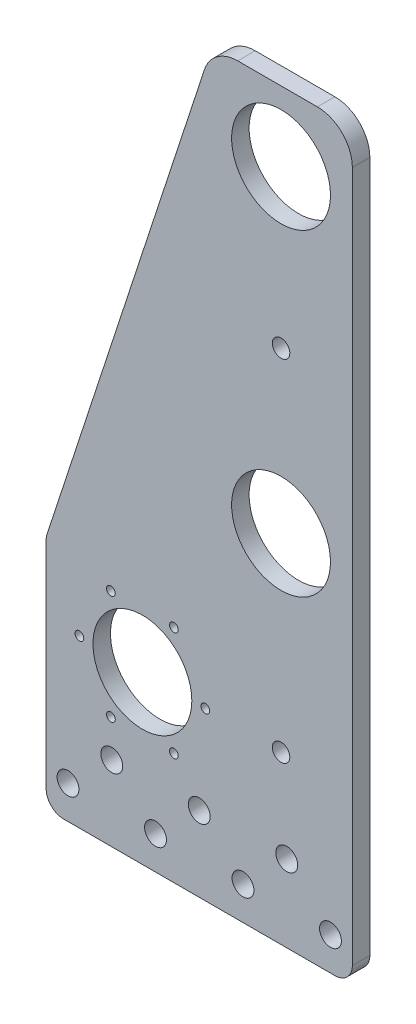
SolidWorks part; units mm, degrees
ref_plane "Front Plane" through (0, 0, 0) normal (0, 0, 1) x (1, 0, 0)
ref_plane "Top Plane" through (0, 0, 0) normal (0, 1, 0) x (1, 0, 0)
ref_plane "Right Plane" through (0, 0, 0) normal (1, 0, 0) x (0, 0, -1)
sketch "Sketch1" plane through (0, 0, 0) normal (0, 0, 1) x (1, 0, 0)
  line L2 (88.9, 205.74) -> (88.9, 5.08)
  line L3 (83.82, 0) -> (5.08, 0)
  line L4 (78.74, 215.9) -> (55.6253, 215.9)
  line L5 (45.9692, 208.9) -> (0.252, 69.2)
  line L6 (0, 67.62) -> (0, 5.08)
  line L7 (6.35, 9.652) -> (31.75, 9.652) construction
  line L8 (27.94, 48.354) -> (27.94, 84.1044) construction
  line L9 (27.94, 48.354) -> (60.7143, 48.354) construction
  circle A0 centre (68.199, 195.58) radius 14.351
  circle A1 centre (68.199, 103.378) radius 14.351
  circle A2 centre (68.199, 149.954) radius 2.54
  circle A3 centre (68.199, 48.354) radius 2.54
  arc A4 (78.74, 215.9) -> (88.9, 205.74) centre (78.74, 205.74) cw
  arc A5 (0, 5.08) -> (5.08, 0) centre (5.08, 5.08) ccw
  arc A6 (88.9, 5.08) -> (83.82, 0) centre (83.82, 5.08) cw
  arc A7 (55.6253, 215.9) -> (45.9692, 208.9) centre (55.6253, 205.74) ccw
  arc A8 (0.252, 69.2) -> (0, 67.62) centre (5.08, 67.62) ccw
  circle A9 centre (27.94, 48.354) radius 14.351
  circle A17 centre (68.199, 195.58) radius 50.8 construction
  circle A18 centre (68.199, 103.378) radius 38.1 construction
  circle A19 centre (6.35, 9.652) radius 3.175
  circle A21 centre (31.75, 9.652) radius 3.175
  circle A22 centre (57.15, 9.652) radius 3.175
  circle A23 centre (82.55, 9.652) radius 3.175
  circle A29 centre (69.85, 22.352) radius 3.175
  circle A30 centre (44.45, 21.844) radius 3.175
  circle A31 centre (19.05, 21.844) radius 3.175
  circle A32 centre (46.228, 48.354) radius 1.27
  circle A33 centre (37.084, 32.5161) radius 1.27
  circle A34 centre (18.796, 32.5161) radius 1.27
  circle A35 centre (9.652, 48.354) radius 1.27
  circle A36 centre (18.796, 64.1919) radius 1.27
  circle A37 centre (37.084, 64.1919) radius 1.27
  point P17 (88.9, 215.9)
  point P20 (0, 0)
  point P23 (88.9, 0)
  point P25 (48.26, 215.9)
  point P26 (48.26, 215.9)
  point P43 (27.94, 48.354)
  point P67 (27.94, 48.354)
  dimension "D1" = 28.702
  dimension "D2" = 28.702
  dimension "D4" = 88.9
  dimension "D7" = 5.08
  dimension "D9" = 5.08
  dimension "D11" = 10.16
  dimension "D12" = 5.08
  dimension "D13" = 10.16
  dimension "D14" = 5.08
  dimension "D16" = 28.702
  dimension "D17" = 18.288
  dimension "D23" = 139.7
  dimension "D24" = 101.6
  dimension "D25" = 76.2
  dimension "D26" = 6.35
  dimension "D29" = 21.844
  dimension "D31" = 6.35
  dimension "D32" = 4
  dimension "D34" = 19.05
  dimension "D39" = 21.844
  dimension "D30" = 6.35
  dimension "D35" = 6.35
  dimension "D37" = 6.35
  dimension "D38" = 25.4
  dimension "D18" = 2.54
  dimension "D3" = 92.202
  dimension ".75" = 20.701
  dimension "D5" = 215.9
  dimension "D6" = 20.32
  dimension "D8" = 45.626
  dimension "D10" = 101.6
  dimension "D15" = 40.64
  dimension "D20" = 27.94
  dimension "D27" = 9.652
  dimension "D28" = 25.4
  dimension "D33" = 12.7
  dimension "D36" = 25.4
  dimension "D19" = 6
extrude "Boss-Extrude1" add sketch "Sketch1" along normal blind 5.08
